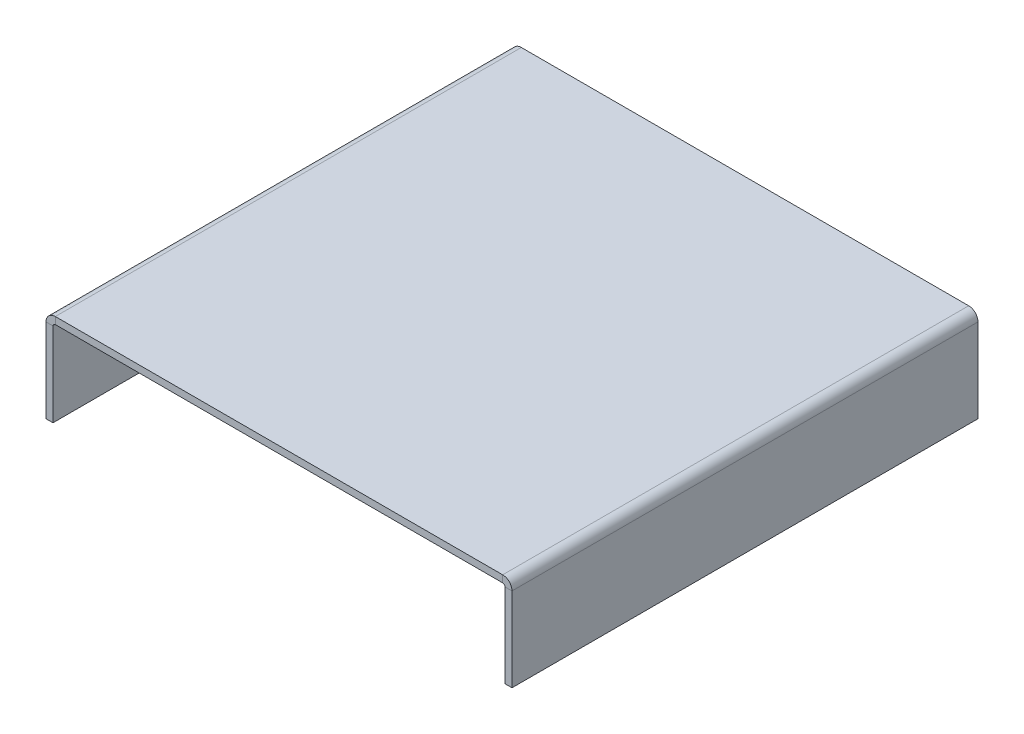
SolidWorks part; units mm, degrees
note: The reader was unsure of these and kept them because the rebuilt part matched: flange length of "Edge-Flange1".
ref_plane "Front Plane" through (0, 0, 0) normal (0, 0, 1) x (1, 0, 0)
ref_plane "Top Plane" through (0, 0, 0) normal (0, 1, 0) x (1, 0, 0)
ref_plane "Right Plane" through (0, 0, 0) normal (1, 0, 0) x (0, 0, -1)
sketch "Sketch1" plane through (0, 0, 0) normal (0, 1, 0) x (1, 0, 0)
  line L1 (50, 50) -> (-50, 50)
  line L2 (50, 50) -> (50, -50)
  line L3 (50, -50) -> (-50, -50)
  line L4 (-50, 50) -> (-50, -50)
  line L5 (50, 50) -> (-50, -50) construction
  line L6 (50, -50) -> (-50, 50) construction
  point P0 (0, 0)
  dimension "D1" = 100
base flange "Base-Flange1" sketch "Sketch1" thickness 1.5 reverse thickness direction no parameters "D1"=0.5
edge flange "Edge-Flange1" sketch "Sketch10" flange profiles "Sketch10", "Sketch11" flange angle 90 flange length 20 flange position material inside bend radius 0.5 thickness 1.5 relief rectangular parameters "D6"=10, "D8"=1
sketch "Sketch10" plane through (50, -1.5, 0) normal (1, 0, 0) x (0, 0, 1)
  line L2 (-50, 0) -> (-50, 18.5)
  line L3 (-50, 18.5) -> (50, 18.5)
  line L4 (50, 18.5) -> (50, 0)
  line L5 (50, 0) -> (-50, 0) construction
  line L6 (50, 0) -> (-50, 0)
sketch "Sketch11" plane through (-50, -1.5, 0) normal (-1, 0, 0) x (0, 0, -1)
  line L0 (50, 0) -> (-50, 0) construction
  line L1 (50, 0) -> (-50, 0)
  line L2 (-50, 0) -> (-50, 18.5)
  line L3 (-50, 18.5) -> (50, 18.5)
  line L4 (50, 18.5) -> (50, 0)
bend "EdgeBend1" bend radius 0.5 bend angle 90 parameters "D5"=1
bend "EdgeBend2" bend radius 0.5 bend angle 90 parameters "D5"=2
sketch "Bend-Lines1" plane through (0, 0, 0) normal (0, 1, 0) x (1, 0, 0)
sketch "Bounding-Box1" plane through (0, 0, 0) normal (0, 1, 0) x (1, 0, 0)
sheet metal parameters "Sheet-Metal1" thickness 1.5 parameters "D1"=0.5
flat pattern "Flat-Pattern1" [suppressed]
sketch "Bend-Lines2" plane through (0, 0, 0) normal (0, 1, 0) x (1, 0, 0)
sketch "Bounding-Box2" [suppressed] plane through (0, 0, 0) normal (0, 1, 0) x (1, 0, 0)
sheet metal parameters "Sheet-Metal2" thickness 1.5 parameters "D1"=0.5
flat pattern "Flat-Pattern1" [suppressed]
sketch "Bend-Lines2" plane through (0, 0, 0) normal (0, 1, 0) x (1, 0, 0)
sketch "Bounding-Box2" [suppressed] plane through (0, 0, 0) normal (0, 1, 0) x (1, 0, 0)
bend of the flat pattern "Flatten-<EdgeBend1>1"
bend of the flat pattern "Flatten-<EdgeBend2>1"
